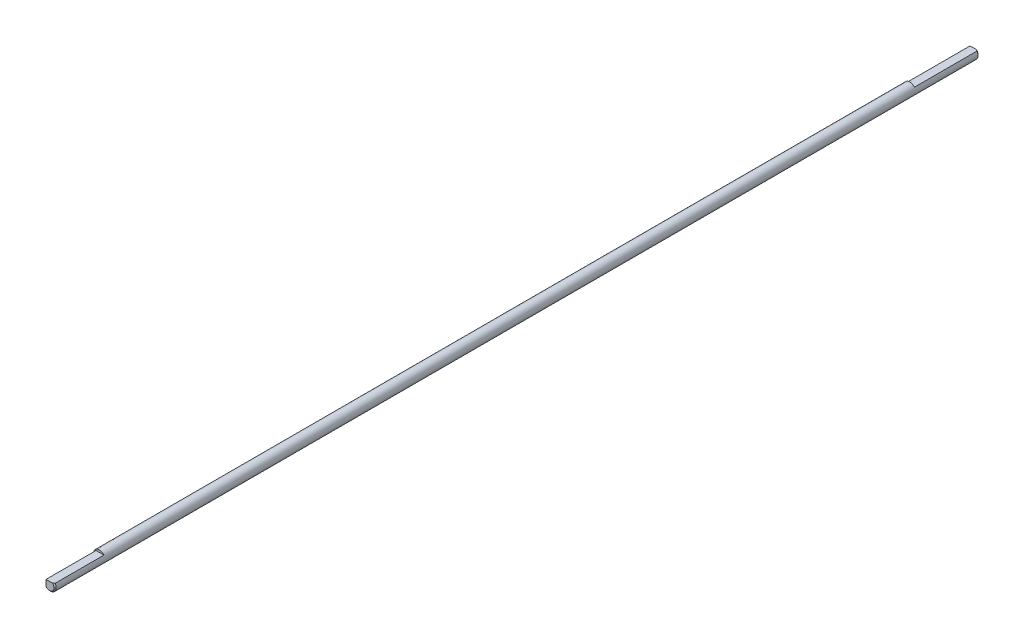
SolidWorks part; units mm, degrees
material "AISI 1020"
ref_plane "Спереди" through (0, 0, 0) normal (0, 0, 1) x (1, 0, 0)
ref_plane "Сверху" through (0, 0, 0) normal (0, 1, 0) x (1, 0, 0)
ref_plane "Справа" through (0, 0, 0) normal (1, 0, 0) x (0, 0, -1)
sketch "Эскиз1" plane through (0, 0, 0) normal (0, 0, 1) x (1, 0, 0)
  circle A0 centre (0, 0) radius 2.5
  dimension "D1" = 5
extrude "Body" add sketch "Эскиз1" along normal blind 406.5
chamfer "ChamferEdges" distance 0.5 angle 45 2 edges at (2.5, 0, 406.5) (2.5, 0, 0)
sketch "Sketch2" plane through (0, 0, 0) normal (1, 0, 0) x (0, 0, -1)
  line L0 (-406.5, 2) -> (-406.5, -2) construction
  line L1 (-28, 4.0099) -> (0.6305, 4.0099)
  line L2 (-28, 4.0099) -> (-28, 1.5)
  line L3 (-28, 1.5) -> (0.6305, 1.5)
  line L4 (0.6305, 4.0099) -> (0.6305, 1.5)
  line L5 (-0.5, 2.5) -> (-406, 2.5) construction
  line L11 (-384.5, 3.4421) -> (-384.5, 1.5)
  line L13 (-412.5, 3.4421) -> (-384.5, 3.4421)
  line L14 (-412.5, 3.4421) -> (-412.5, 1.5)
  line L15 (-412.5, 1.5) -> (-384.5, 1.5)
  point P4 (-384.7285, 3.4421)
  point P5 (-384.5, 1.3012)
  dimension "D1" = 28
  dimension "D3" = 1
  dimension "D4" = 22
extrude "FirstSlots" cut sketch "Sketch2" against normal through all both and the other way through all
pattern_circular "CirPattern1" count 2 every 90 about axis through (0, 0, 406.5) along (0, 0, 1) of "FirstSlots"
